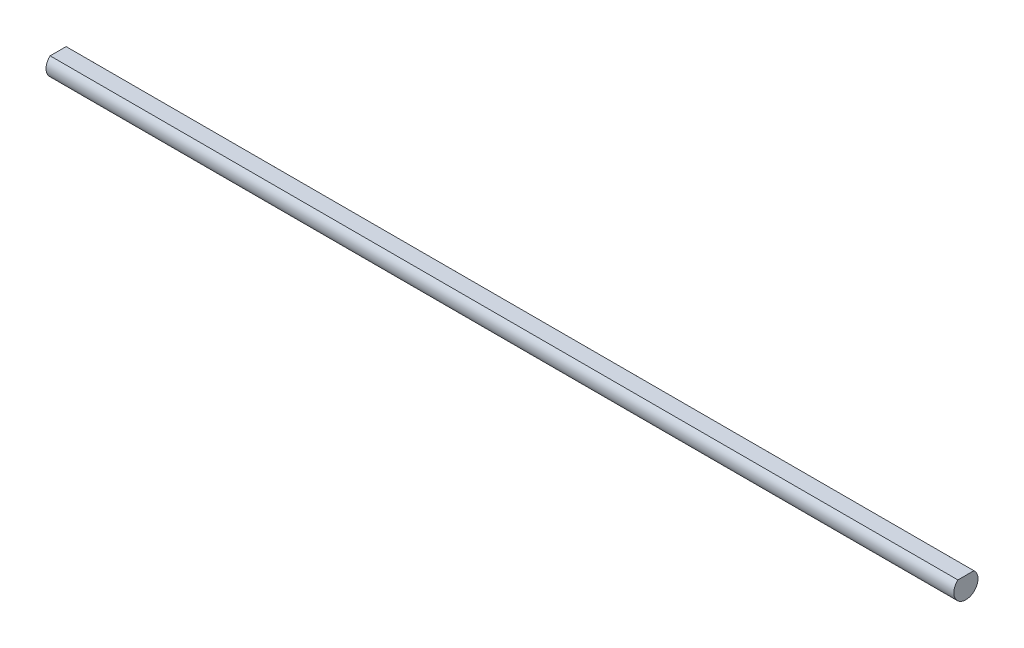
SolidWorks part; units mm, degrees
ref_plane "Front Plane" through (0, 0, 0) normal (0, 0, 1) x (1, 0, 0)
ref_plane "Top Plane" through (0, 0, 0) normal (0, 1, 0) x (1, 0, 0)
ref_plane "Right Plane" through (0, 0, 0) normal (1, 0, 0) x (0, 0, -1)
sketch "Sketch1" plane through (0, 0, 0) normal (1, 0, 0) x (0, 0, -1)
  line L0 (-1.3229, 1.5) -> (1.3229, 1.5)
  arc A0 (-1.3229, 1.5) -> (1.3229, 1.5) centre (0, 0) ccw
  dimension "D1" = 4
  dimension "D2" = 1.5
extrude "Boss-Extrude1" add sketch "Sketch1" along normal mid plane 150
